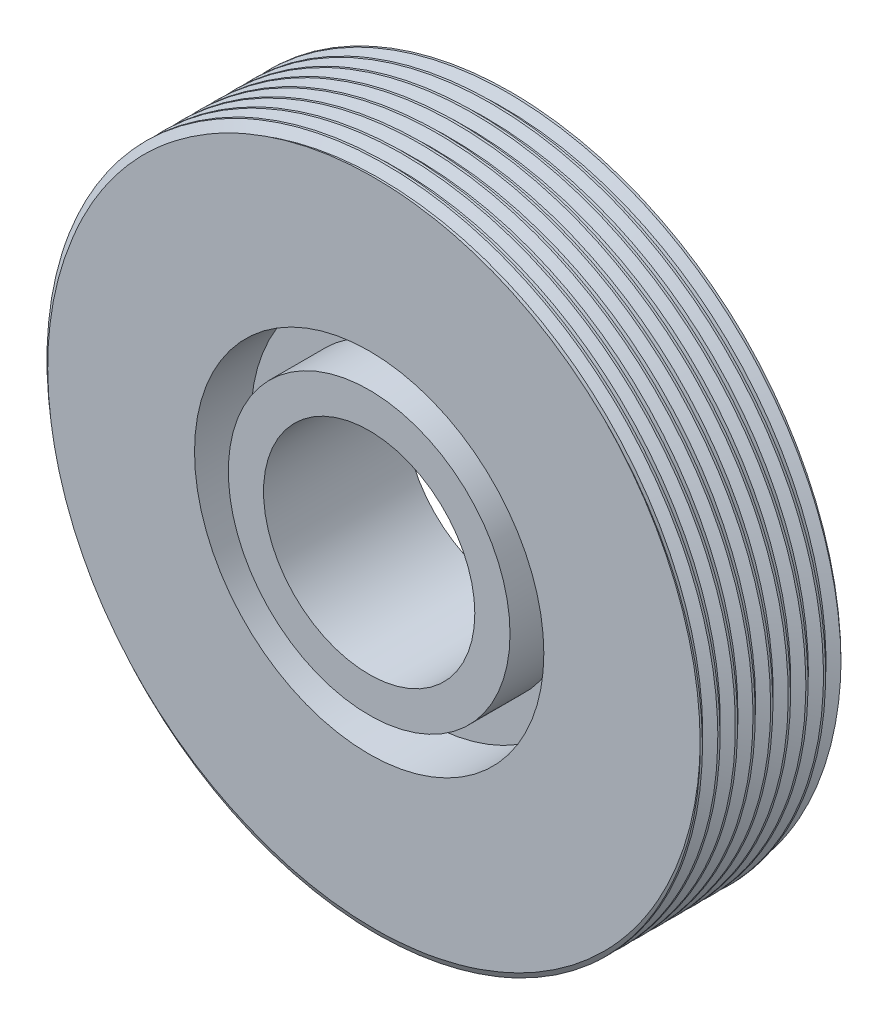
SolidWorks part; units mm, degrees
ref_plane "Front Plane" through (0, 0, 0) normal (0, 0, 1) x (1, 0, 0)
ref_plane "Top Plane" through (0, 0, 0) normal (0, 1, 0) x (1, 0, 0)
ref_plane "Right Plane" through (0, 0, 0) normal (1, 0, 0) x (0, 0, -1)
sketch "Sketch3" plane through (0, 0, 0) normal (0, 0, 1) x (1, 0, 0)
  circle A3 centre (8.3476, 27.7238) radius 14.9225
  dimension "D1" = 29.845
extrude "Boss-Extrude1" add sketch "Sketch3" against normal blind 6.35 contours A3 region at (8.3476, 27.7238, 0)
sketch "Sketch11" plane through (0, 0, 0) normal (0, 0, 1) x (1, 0, 0)
  circle A0 centre (8.3476, 27.7238) radius 4.7625
extrude "Cut-Extrude3" cut sketch "Sketch11" against normal through all
sketch "Sketch12" plane through (0, 0, 0) normal (0, 0, 1) x (1, 0, 0)
  circle A0 centre (8.3476, 27.7238) radius 6.35
  circle A1 centre (8.3476, 27.7238) radius 7.874
  dimension "D1" = 15.748
  dimension "D2" = 1.524
extrude "Cut-Extrude4" cut sketch "Sketch12" against normal blind 2.54
thread "Thread1" pitch 0.7937 method cut profile "Thread Profile1" start angle 0, offset 0.7937, length 7.62, pitch 0.7937, diameter 29.845
ref_plane "Plane1" through (23.2701, 27.7238, -7.1437) normal (0, -1, 0) x (1, 0, 0)
sketch "Thread Profile1" plane through (23.2701, 27.7238, -7.1437) normal (0, -1, 0) x (1, 0, 0)
  line L0 (0, 0) -> (0, 0.7937) construction
  line L11 (0, 0) -> (0, 0.6945)
  line L12 (0, 0.6945) -> (-0.4296, 0.4465)
  line L13 (-0.4296, 0.4465) -> (-0.4296, 0.248)
  line L15 (-0.4296, 0.248) -> (0, 0)
  line L17 (-0.4296, 0.3473) -> (0, 0.3473) construction
  point P2 (0, 0)
  dimension "Pitch" = 0.7937
  dimension "Profile_Angle" = 60
  dimension "Profile_Land" = 0.1984
  dimension "Profile_Height" = 0.4296
